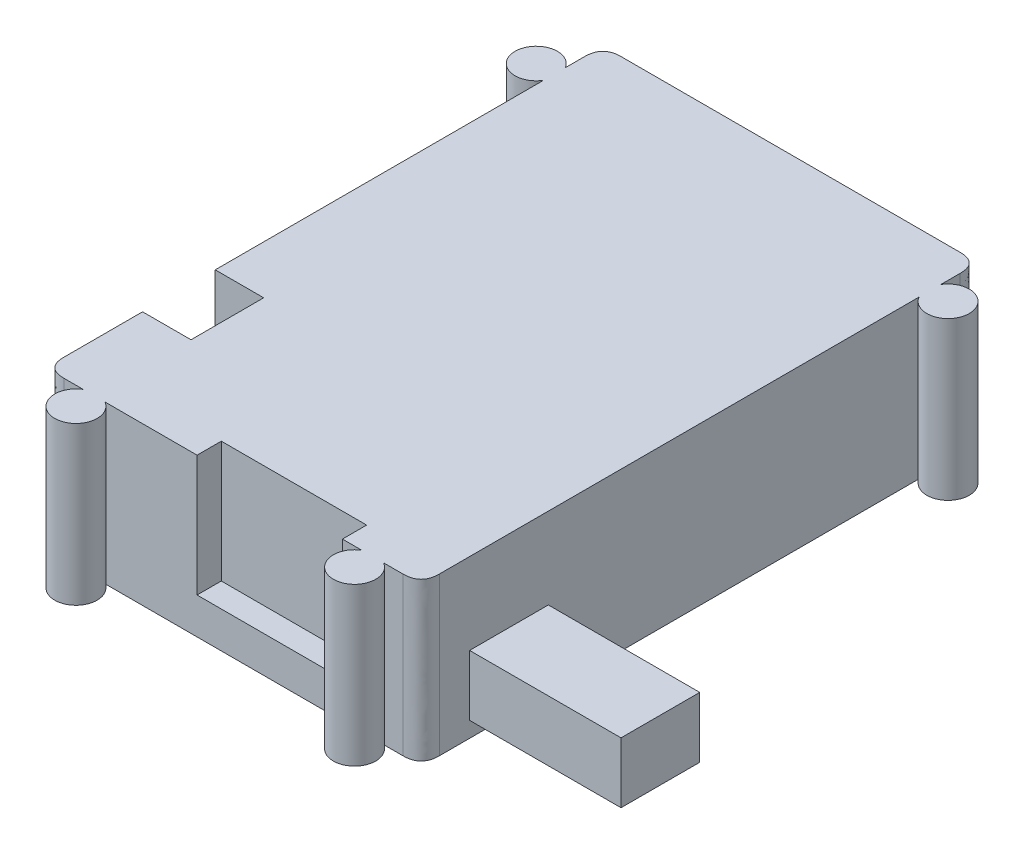
SolidWorks part; units mm, degrees
ref_plane "Alzado" through (0, 0, 0) normal (0, 0, 1) x (1, 0, 0)
ref_plane "Planta" through (0, 0, 0) normal (0, 1, 0) x (1, 0, 0)
ref_plane "Vista lateral" through (0, 0, 0) normal (1, 0, 0) x (0, 0, -1)
sketch "Croquis1" plane through (0, 0, 0) normal (0, 1, 0) x (1, 0, 0)
  line L0 (0, 0) -> (0, 63.7038) construction
  line L1 (-31, 46) -> (31, 46)
  line L2 (-31, 46) -> (-31, -46)
  line L3 (-31, -46) -> (31, -46)
  line L4 (31, 46) -> (31, -46)
  line L5 (-31, 46) -> (31, -46) construction
  line L6 (-31, -46) -> (31, 46) construction
  circle A0 centre (34, 38) radius 3.5
  circle A1 centre (23, -49) radius 3.5
  circle A2 centre (-34, 38) radius 3.5
  circle A3 centre (-23, -49) radius 3.5
  point P0 (0, 0)
  dimension "D4" = 7
  dimension "D6" = 7
  dimension "D1" = 62
  dimension "D2" = 92
  dimension "D3" = 3
  dimension "D5" = 8
  dimension "D7" = 8
  dimension "D8" = 3
extrude "Saliente-Extruir1" add sketch "Croquis1" along normal blind 26 contours L3 A3 A1 L4 A0 L1 L2 A2 | A3 L3 | A1 | A0 | L2 L3 L4 L1 | A2 region at (0, 0, -0.0033) region at (-23, 0, 49.1048)
fillet "Redondeo1" radius 3 4 edges at (31, 13, 46) (-31, 13, 46) (-31, 13, -46) (31, 13, -46) conic rho 0.5
sketch "Croquis2" plane through (31, 0, 0) normal (1, 0, 0) x (0, 0, -1)
  line L0 (-43, 26) -> (-43, 0) construction
  line L1 (-38, 12.5757) -> (-25, 12.5757)
  line L2 (-38, 12.5757) -> (-38, 2.5757)
  line L3 (-38, 2.5757) -> (-25, 2.5757)
  line L4 (-25, 12.5757) -> (-25, 2.5757)
  line L5 (-38, 12.5757) -> (-25, 2.5757) construction
  line L6 (-38, 2.5757) -> (-25, 12.5757) construction
  point P0 (-31.5, 7.5757)
  dimension "D1" = 13
  dimension "D2" = 10
  dimension "D3" = 18
extrude "Cortar-Extruir1" cut sketch "Croquis2" against normal blind 20
sketch "Croquis3" plane through (0, 26, 0) normal (0, 1, 0) x (1, 0, 0)
  line L0 (-31, 36.1972) -> (-31, -43) construction
  line L1 (-31, -30) -> (-23, -30)
  line L2 (-31, -30) -> (-31, -18)
  line L3 (-31, -18) -> (-23, -18)
  line L4 (-23, -30) -> (-23, -18)
  line L5 (-28, -46) -> (-24.8028, -46) construction
  point P8 (-26.4014, -46)
  dimension "D1" = 12
  dimension "D2" = 8
  dimension "D3" = 16
extrude "Cortar-Extruir2" cut sketch "Croquis3" against normal blind 20
sketch "Croquis4" plane through (0, 26, 0) normal (0, 1, 0) x (1, 0, 0)
  line L0 (-21.1972, -46) -> (21.1972, -46) construction
  line L1 (-6, -46) -> (18, -46)
  line L2 (-6, -46) -> (-6, -42)
  line L3 (-6, -42) -> (18, -42)
  line L4 (18, -46) -> (18, -42)
  line L5 (-31, -30) -> (-31, -43) construction
  dimension "D1" = 24
  dimension "D2" = 4
  dimension "D3" = 25
extrude "Cortar-Extruir3" cut sketch "Croquis4" against normal blind 20
sketch "Croquis5" plane through (31, 0, 0) normal (1, 0, 0) x (0, 0, -1)
  line L1 (-38, 2.5757) -> (-25, 2.5757)
  line L2 (-38, 2.5757) -> (-38, 12.5757)
  line L3 (-38, 12.5757) -> (-25, 12.5757)
  line L4 (-25, 2.5757) -> (-25, 12.5757)
extrude "Saliente-Extruir2" add sketch "Croquis5" along normal blind 25 separate body
